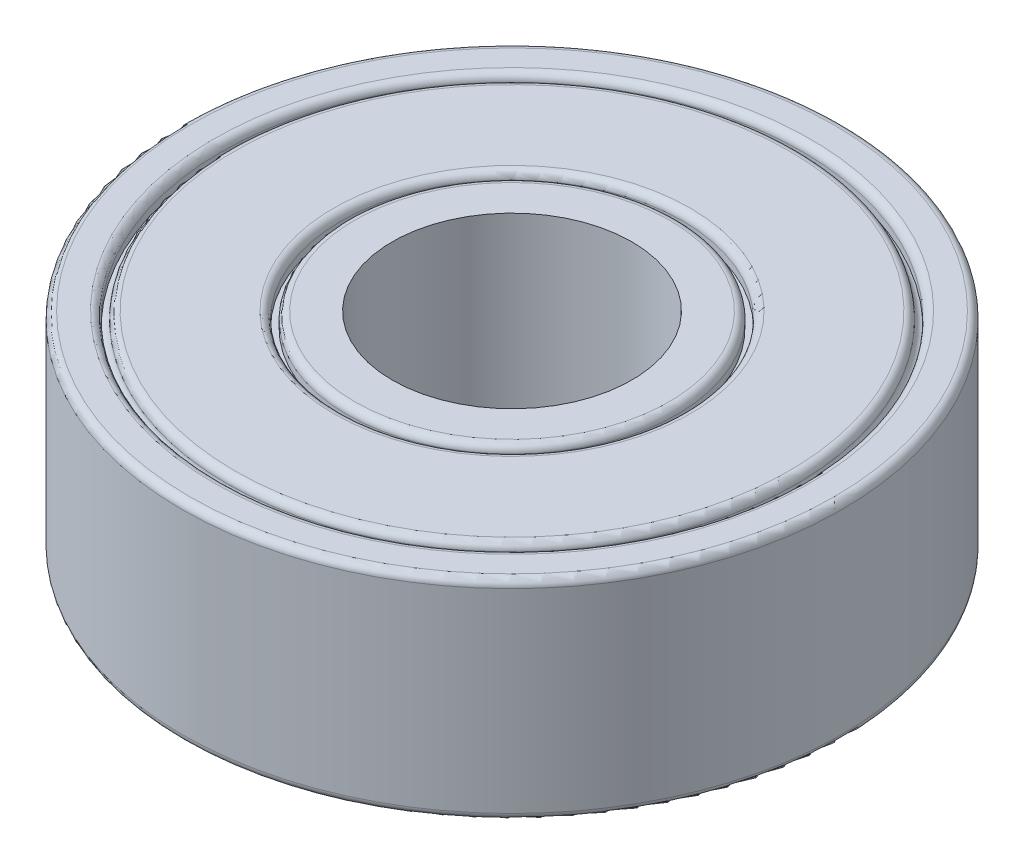
SolidWorks part; units mm, degrees
material "Chrome Stainless Steel"
ref_plane "Front Plane" through (0, 0, 0) normal (0, 0, 1) x (1, 0, 0)
ref_plane "Top Plane" through (0, 0, 0) normal (0, 1, 0) x (1, 0, 0)
ref_plane "Right Plane" through (0, 0, 0) normal (1, 0, 0) x (0, 0, -1)
sketch "Sketch1" plane through (0, 0, 0) normal (0, 1, 0) x (1, 0, 0)
  circle A0 centre (0, 0) radius 4
  circle A1 centre (0, 0) radius 11
  dimension "D1" = 8
  dimension "D2" = 22
extrude "Boss-Extrude1" add sketch "Sketch1" along normal blind 7
sketch "Sketch2" plane through (0, 7, 0) normal (0, 1, 0) x (1, 0, 0)
  circle A1 centre (0, 0) radius 5.7
  circle A2 centre (0, 0) radius 9.7
  circle A3 centre (0, 0) radius 9.5
  circle A4 centre (0, 0) radius 9.5
  circle A6 centre (0, 0) radius 5.5
  circle A7 centre (0, 0) radius 5.5
  dimension "D1" = 1.5
  dimension "D2" = 0.2
  dimension "D3" = 1.5
  dimension "D4" = 0.2
extrude "Cut-Extrude1" cut sketch "Sketch2" against normal blind 0.5 contours A2 A4 | A1 A7 region at (-5.5388, 7, 0) region at (-9.6726, 7, 0)
ref_plane "Plane1" through (0, 3.5, 0) normal (0, 1, 0) x (1, 0, 0)
mirror "Mirror1" about plane through (0, 3.5, 0) normal (0, 1, 0) of "Cut-Extrude1"
fillet "Fillet1" radius 0.25 9 edges at (0, 7, 9.5) (0, 7, 9.7) (0, 6.5, 9.5) (0, 7, 5.5) (0, 7, 5.7) (0, 0, 5.5) (0, 0, 5.7) (0, 0, 9.5) (0, 0, 9.7)
fillet "Fillet2" radius 0.25 2 edges at (0, 7, 11) (0, 0, 11)
